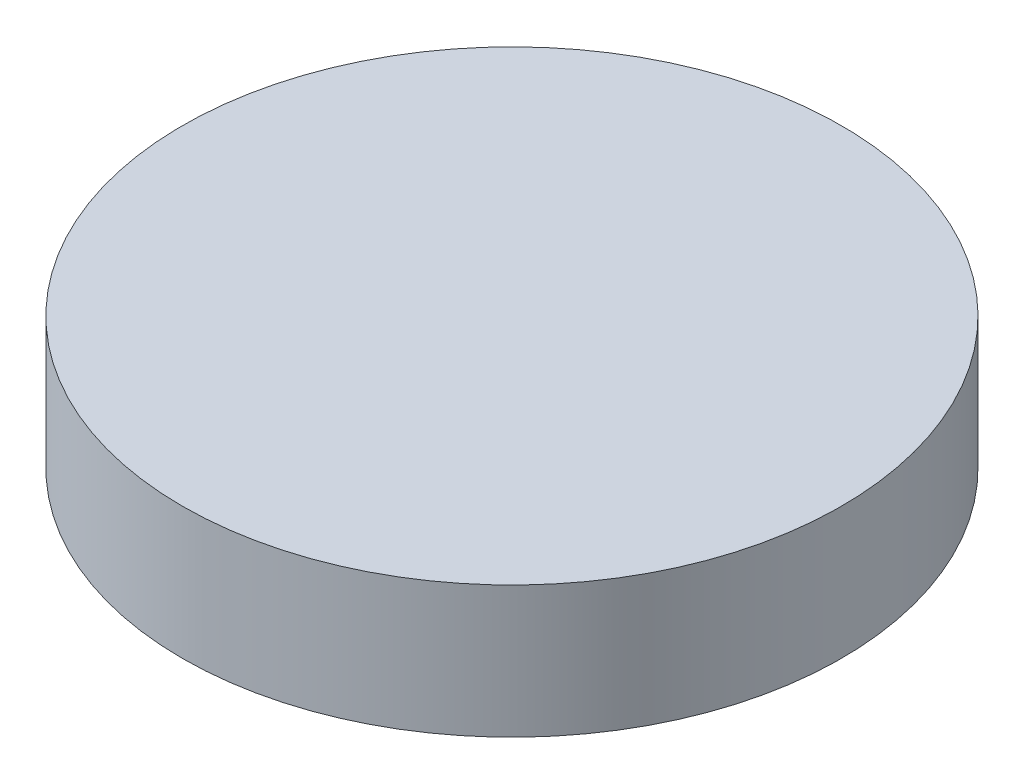
SolidWorks part; units mm, degrees
ref_plane "Front Plane" through (0, 0, 0) normal (0, 0, 1) x (1, 0, 0)
ref_plane "Top Plane" through (0, 0, 0) normal (0, 1, 0) x (1, 0, 0)
ref_plane "Right Plane" through (0, 0, 0) normal (1, 0, 0) x (0, 0, -1)
sketch "Sketch1" plane through (0, 0, 0) normal (0, 1, 0) x (1, 0, 0)
  circle A0 centre (0, 0) radius 25
  dimension "D1" = 50
extrude "Boss-Extrude1" add sketch "Sketch1" along normal blind 10
ref_axis "HeadAxis" through (0, 10, 0) along (0, -1, 0)
ref_point "BaseOrigin"
